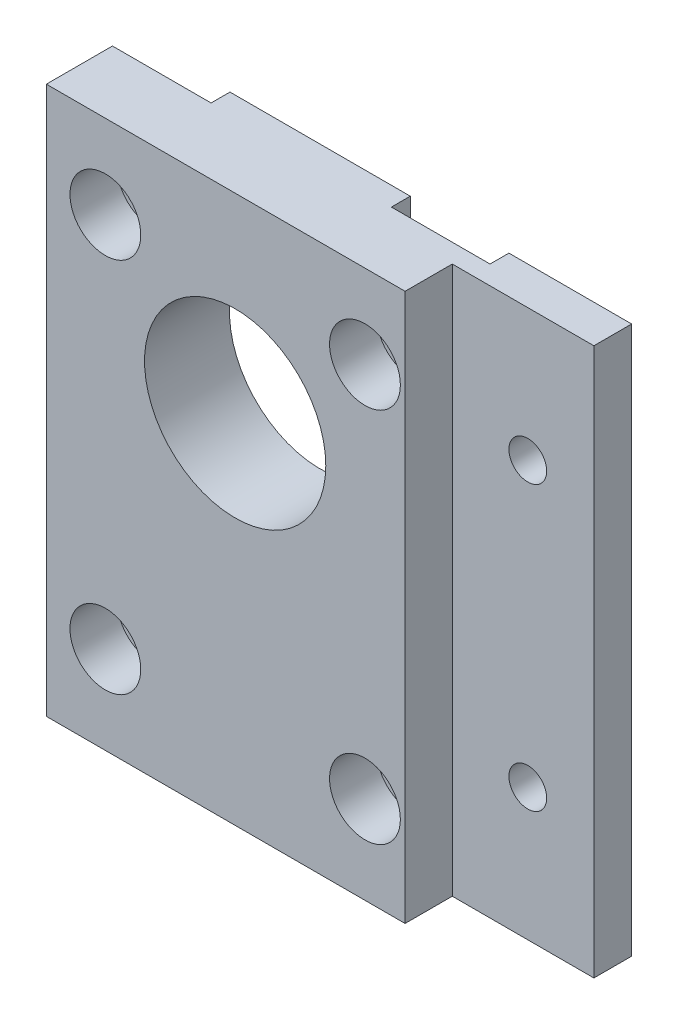
SolidWorks part; units mm, degrees
material "1060 Alloy"
ref_plane "Front Plane" through (0, 0, 0) normal (0, 0, 1) x (1, 0, 0)
ref_plane "Top Plane" through (0, 0, 0) normal (0, 1, 0) x (1, 0, 0)
ref_plane "Right Plane" through (0, 0, 0) normal (1, 0, 0) x (0, 0, -1)
sketch "Sketch1" plane through (0, 0, 0) normal (0, 0, 1) x (1, 0, 0)
  line L0 (-13.75, -19.7) -> (-9.6769, -16.8) construction
  line L3 (20, 29) -> (33, 29)
  line L8 (20, -29) -> (-20, -29)
  line L9 (20, -29) -> (20, 29) construction
  line L10 (33, 29) -> (33, -29)
  line L11 (20, 29) -> (-20, 29)
  line L14 (-20, -29) -> (-20, 29)
  line L15 (20, -29) -> (-20, 29) construction
  line L16 (20, 29) -> (-20, -29) construction
  line L17 (-16.186, -16.2786) -> (-12.1129, -13.3786)
  line L18 (-11.314, -23.1214) -> (-7.2409, -20.2214)
  line L19 (0, -29) -> (0, 29) construction
  line L22 (33, -29) -> (20, -29)
  line L23 (17.2075, -17.3155) -> (20, -21.3647)
  line L24 (9.55, -19.7) -> (9.55, -29)
  line L25 (-9.55, 20.15) -> (-9.55, 29)
  line L26 (-17.2075, 17.7655) -> (-20, 21.8147)
  line L27 (9.55, 20.15) -> (9.55, 29)
  line L28 (17.2075, 17.7655) -> (20, 21.8147)
  line L29 (20, 21.8147) -> (20, 29)
  line L30 (-16.186, -16.2786) -> (-20, -16.2786)
  line L31 (20, -29) -> (20, -21.3647)
  line L32 (-11.314, -29) -> (-11.314, -23.1214)
  circle A18 centre (-13.75, 20.15) radius 4.2
  circle A19 centre (13.75, 20.15) radius 4.2
  circle A20 centre (13.75, -19.7) radius 4.2
  arc A21 (-16.186, -16.2786) -> (-11.314, -23.1214) centre (-13.75, -19.7) ccw
  arc A22 (-7.2409, -20.2214) -> (-12.1129, -13.3786) centre (-9.6769, -16.8) ccw
  circle A23 centre (0, 8.8) radius 9.6
  circle A24 centre (-5.725, -6.1) radius 4.2
  circle A25 centre (5.725, -6.1) radius 4.2
  point P0 (0, 0)
  point P14 (-6.2555, -14.364)
  point P31 (-11.7135, -18.25)
  point P37 (5.725, -10.3)
  point P43 (20, 29)
  point P46 (-20, 29)
  dimension "D1" = 58
  dimension "D2" = 40
  dimension "D3" = 12.2
  dimension "D4" = 8.4
  dimension "D5" = 8.4
  dimension "D6" = 19.2
  dimension "D7" = 9.3
  dimension "D8" = 27.5
  dimension "D9" = 39.85
  dimension "D10" = 5
  dimension "D12" = 20.2
  dimension "D13" = 11.45
  dimension "D14" = 22.9
  dimension "D15" = 13
extrude "Boss-Extrude1" add sketch "Sketch1" along normal blind 2 contours L11 L14 L8 L9 A25 A24 A23 A22 L18 A21 L17 A20 A19 A18 region at (9.5102, -0.5461, 0)
sketch "Sketch4" plane through (0, 0, 2) normal (0, 0, 1) x (1, 0, 0)
  line L0 (0, -29) -> (0, 29) construction
  line L6 (33, -29) -> (20, -29) construction
  line L8 (-20, -29) -> (33, -29)
  line L11 (33, -29) -> (33, 29)
  line L12 (-20, 29) -> (-20, -29)
  line L13 (-20, -16.2786) -> (-20, 21.8147) construction
  line L14 (-20, 29) -> (33, 29)
  line L15 (20, 29) -> (33, 29) construction
  line L16 (33, 29) -> (33, -29) construction
  circle A2 centre (13.75, -19.7) radius 2
  circle A3 centre (-13.75, 20.15) radius 2
  circle A4 centre (13.75, 20.15) radius 2
  circle A10 centre (-13.75, -19.7) radius 2
  circle A11 centre (0, 8.8) radius 9.6
  circle A12 centre (0, 8.8) radius 9.6 construction
  dimension "D1" = 4
extrude "Boss-Extrude3" add sketch "Sketch4" along normal blind 2
sketch "Sketch5" plane through (0, 0, 4) normal (0, 0, 1) x (1, 0, 0)
  line L0 (-20, 0) -> (33, 0) construction
  line L3 (-20, 29) -> (-20, -29) construction
  line L4 (33, -29) -> (33, 29) construction
  circle A0 centre (26, 15) radius 2
  circle A1 centre (26, -15) radius 2
  dimension "D1" = 4
  dimension "D2" = 15
  dimension "D3" = 7
extrude "Cut-Extrude1" cut sketch "Sketch5" against normal blind 4
ref_plane "Plane1" through (0, 0, 0) normal (0, 0, -1) x (-1, 0, 0)
sketch "Sketch6" plane through (0, 0, 4) normal (0, 0, 1) x (1, 0, 0)
  line L0 (18, 29) -> (18, -29)
  line L1 (33, 29) -> (-20, 29) construction
  line L2 (-20, -29) -> (33, -29) construction
  line L3 (33, -29) -> (33, 29) construction
  circle A52 centre (-13.75, 20.15) radius 3.75
  circle A53 centre (13.75, 20.15) radius 3.75
  circle A54 centre (26, 15) radius 2
  circle A55 centre (13.75, -19.7) radius 3.75
  circle A56 centre (-13.75, -19.7) radius 3.75
  circle A57 centre (26, -15) radius 2
  circle A59 centre (26, 15) radius 2 construction
  circle A60 centre (26, -15) radius 2 construction
  line M5 (-20, 29) -> (-20, -29)
  line M6 (-20, -29) -> (33, -29)
  line M7 (33, -29) -> (33, 29)
  line M8 (33, 29) -> (-20, 29)
  circle M11 centre (0, 8.8) radius 9.6
  dimension "D1" = 7.5
  dimension "D2" = 15
extrude "Boss-Extrude4" add sketch "Sketch6" along normal blind 5 contours A57 A56 A55 A54 A53 A52 M8 M5 M6 M7 M11 region at (-1.2683, -1.4891, 4)
